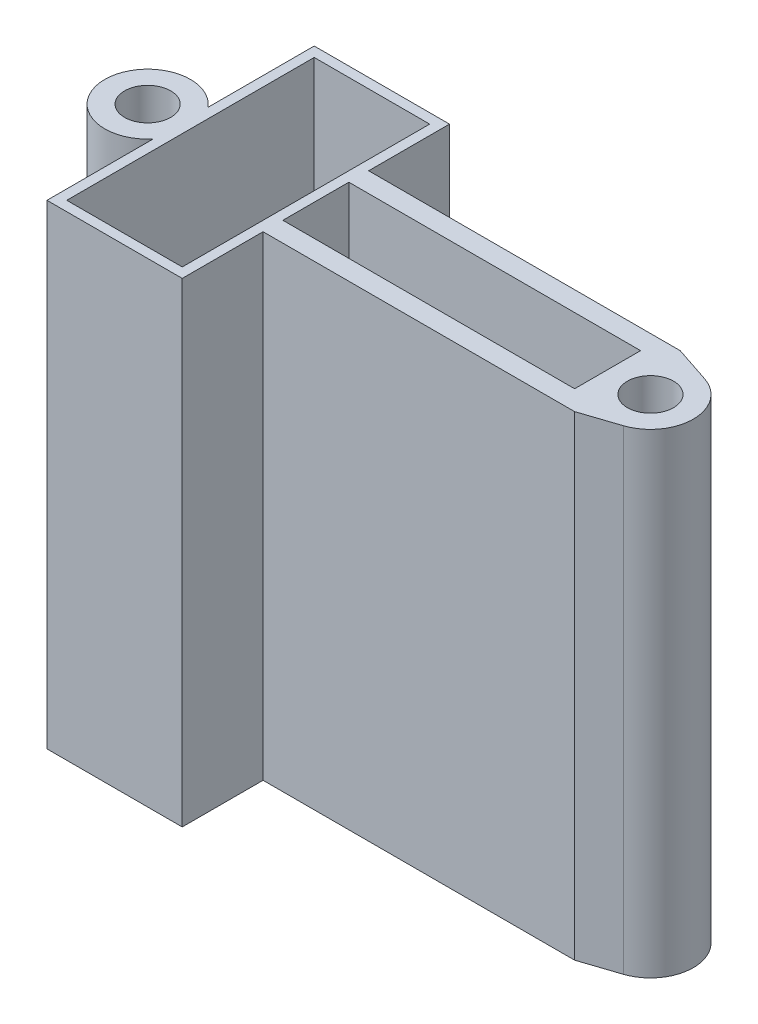
SolidWorks part; units mm, degrees
ref_plane "Front Plane" through (0, 0, 0) normal (0, 0, 1) x (1, 0, 0)
ref_plane "Top Plane" through (0, 0, 0) normal (0, 1, 0) x (1, 0, 0)
ref_plane "Right Plane" through (0, 0, 0) normal (1, 0, 0) x (0, 0, -1)
sketch "Sketch1" plane through (0, 0, 0) normal (0, 1, 0) x (1, 0, 0)
  line L0 (-38.1, 0) -> (38.1, 0) construction
  circle A0 centre (0, 0) radius 57.15
  circle A1 centre (-38.1, 0) radius 3.4925
  circle A2 centre (38.1, 0) radius 3.4925
  circle A3 centre (0, 0) radius 4
  point P7 (0, 0)
  dimension "D1" = 114.3
  dimension "D2" = 6.985
  dimension "D4" = 8
  dimension "D3" = 76.2
sketch "Sketch2" plane through (0, 0, 0) normal (0, 1, 0) x (1, 0, 0)
  line L0 (-33.1075, 20.25) -> (-12.6075, 20.25)
  line L1 (-31.6075, 18.75) -> (-14.1075, 18.75)
  line L2 (-31.6075, 18.75) -> (-31.6075, -18.75)
  line L3 (-31.6075, -18.75) -> (-14.1075, -18.75)
  line L4 (-14.1075, 18.75) -> (-14.1075, -18.75)
  line L5 (-12.6075, 20.25) -> (-12.6075, 8)
  line L6 (-33.1075, -20.25) -> (-12.6075, -20.25)
  line L7 (-33.1075, 20.25) -> (-33.1075, 4.1506)
  line L8 (-12.6075, 8) -> (34.6075, 8)
  line L9 (-12.6075, 5) -> (31.6075, 5)
  line L10 (-12.6075, 5) -> (-12.6075, -5)
  line L11 (-12.6075, -5) -> (31.6075, -5)
  line L12 (31.6075, 5) -> (31.6075, -5)
  line L14 (-12.6075, -8) -> (34.6075, -8)
  line L16 (34.6075, 8) -> (40.1452, 6.1619)
  line L17 (34.6075, -8) -> (40.1452, -6.1619)
  line L18 (-33.1075, -4.1506) -> (-33.1075, -20.25)
  line L19 (-33.1075, 20.25) -> (-33.1075, -20.25) construction
  line L20 (-15.6075, 8) -> (34.6075, 8) construction
  line L21 (-15.6075, 8) -> (-15.6075, -8) construction
  line L22 (-15.6075, -8) -> (34.6075, -8) construction
  line L24 (-12.6075, 20.25) -> (-12.6075, -20.25) construction
  line L25 (-12.6075, -8) -> (-12.6075, -20.25)
  line L26 (34.6075, 8) -> (34.6075, -8) construction
  circle A0 centre (-38.1, 0) radius 3.4925 construction
  circle A1 centre (38.1, 0) radius 3.4925 construction
  circle A2 centre (38.1, 0) radius 6.4925 construction
  circle A3 centre (0, 0) radius 4 construction
  circle A4 centre (-38.1, 0) radius 6.4925 construction
  circle A13 centre (38.1, 0) radius 3.4925
  circle A14 centre (-38.1, 0) radius 3.4925
  arc A15 (-33.1075, 4.1506) -> (-33.1075, -4.1506) centre (-38.1, 0) ccw
  arc A16 (40.1452, -6.1619) -> (40.1452, 6.1619) centre (38.1, 0) ccw
  point P12 (-31.6075, 0)
  point P21 (31.6075, 0)
  dimension "D2" = 37.5
  dimension "D3" = 17.5
  dimension "D5" = 5
  dimension "D1" = 3
  dimension "D4" = 1.5
  dimension "D6" = 3
extrude "Boss-Extrude2" add sketch "Sketch2" along normal blind 72
